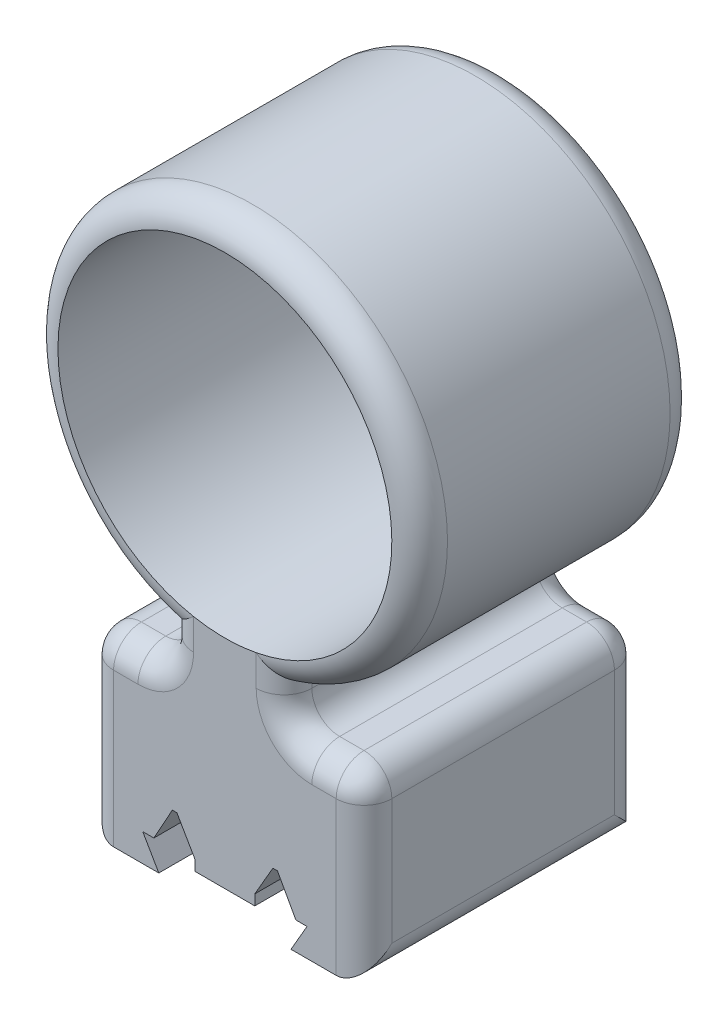
SolidWorks part; units mm, degrees
material "6061-T4 (SS)"
ref_plane "Front Plane" through (0, 0, 0) normal (0, 0, 1) x (1, 0, 0)
ref_plane "Top Plane" through (0, 0, 0) normal (0, 1, 0) x (1, 0, 0)
ref_plane "Right Plane" through (0, 0, 0) normal (1, 0, 0) x (0, 0, -1)
sketch "Sketch1" plane through (0, 0, 0) normal (0, 0, 1) x (1, 0, 0)
  line L0 (-4.75, 0) -> (-10, 0)
  line L1 (-10, 0) -> (-10, 13)
  line L2 (-10, 13) -> (-4.25, 13)
  line L3 (-4.25, 13) -> (-4.25, 15.6607)
  line L4 (-4.75, 0) -> (-5.905, 2)
  line L5 (-5.905, 2) -> (-5.105, 2)
  line L6 (-5.105, 2) -> (-3.779, 4.4)
  line L7 (-3.779, 4.4) -> (-3.449, 4.4)
  line L8 (-3.449, 4.4) -> (-2.15, 2.15)
  line L9 (-2.15, 2.15) -> (-2.15, 1.4)
  line L10 (-2.15, 1.4) -> (2.15, 1.4)
  line L11 (0, 0) -> (0, 32.2772) construction
  line L12 (2.15, 2.15) -> (2.15, 1.4)
  line L13 (3.449, 4.4) -> (2.15, 2.15)
  line L14 (3.779, 4.4) -> (3.449, 4.4)
  line L15 (5.105, 2) -> (3.779, 4.4)
  line L16 (5.905, 2) -> (5.105, 2)
  line L17 (4.75, 0) -> (5.905, 2)
  line L18 (4.75, 0) -> (10, 0)
  line L19 (10, 0) -> (10, 13)
  line L20 (10, 13) -> (4.25, 13)
  line L21 (4.25, 13) -> (4.25, 15.6607)
  circle A0 centre (0, 29) radius 12
  arc A1 (4.25, 15.6607) -> (-4.25, 15.6607) centre (0, 29) ccw
  point P6 (4.25, 14.3303)
  point P13 (0, 1.4)
  dimension "D1" = 0.75
  dimension "D13" = 16
  dimension "D14" = 24
  dimension "D15" = 28
  dimension "D2" = 0.33
  dimension "D3" = 2.4
  dimension "D4" = 2
  dimension "D5" = 0.8
  dimension "D6" = 4.3
  dimension "D7" = 13
  dimension "D8" = 1.4
  dimension "D9" = 9.5
  dimension "D10" = 11.81
  dimension "D11" = 20
  dimension "D12" = 60
  dimension "D16" = 8.5
extrude "Boss-Extrude1" add sketch "Sketch1" along normal mid plane 20
fillet "Fillet1" radius 2 20 edges at (-10, 13, 0) (-10, 6.5, 10) (-10, 0, 0) (-10, 6.5, -10) (10, 0, 0) (10, 6.5, 10) (10, 13, 0) (10, 6.5, -10) (0, 43, 10) (0, 43, -10) (4.25, 14.3303, 10) (4.25, 14.3303, -10) (-4.25, 14.3303, -10) (4.25, 13, 0) (7.125, 13, 10) (7.125, 13, -10) (-7.125, 13, -10) (-4.25, 13, 0) (-7.125, 13, 10) (-4.25, 14.3303, 10)
